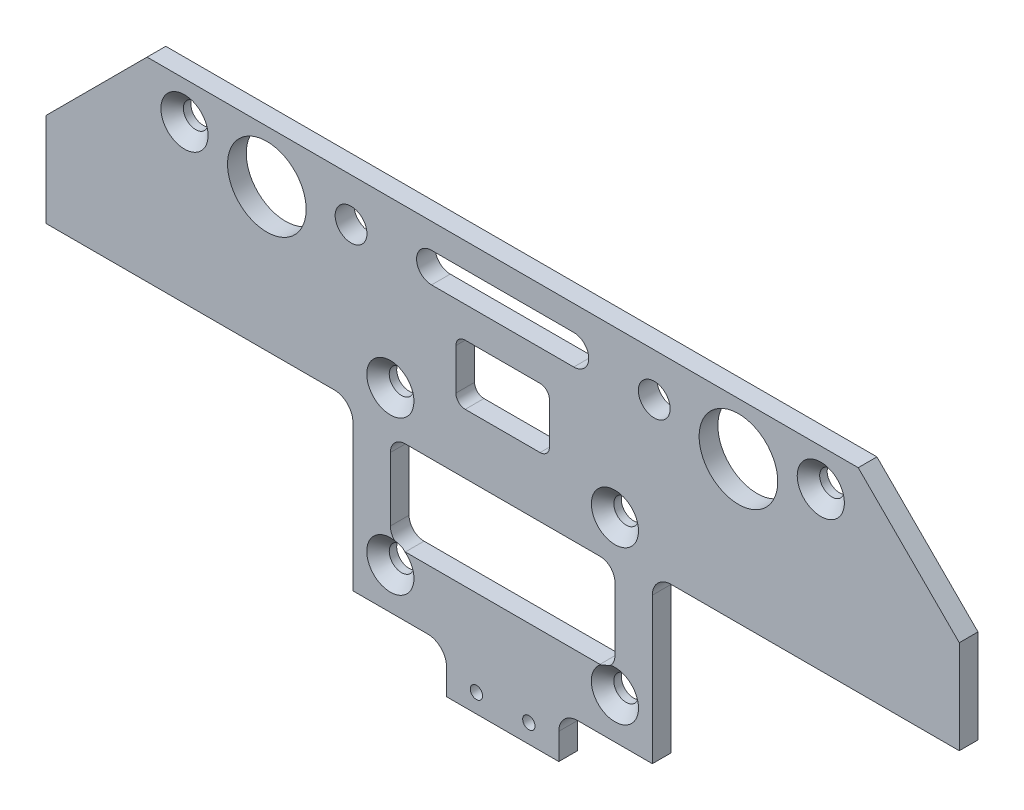
SolidWorks part; units mm, degrees
material "3.0205 (EN AW-1200)"
ref_plane "Plan de face" through (0, 0, 0) normal (0, 0, 1) x (1, 0, 0)
ref_plane "Plan de dessus" through (0, 0, 0) normal (0, 1, 0) x (1, 0, 0)
ref_plane "Plan de droite" through (0, 0, 0) normal (1, 0, 0) x (0, 0, -1)
sketch "Esquisse1" plane through (0, 0, 0) normal (0, 0, 1) x (1, 0, 0)
  line L0 (0, 0) -> (0, -52)
  line L1 (0, 0) -> (190, 0)
  line L2 (190, 0) -> (190, -52)
  line L3 (190, -52) -> (135, -52)
  line L4 (135, -52) -> (135, -96)
  line L5 (110, -108) -> (80, -108)
  line L6 (55, -96) -> (55, -52)
  line L7 (55, -52) -> (0, -52)
  line L9 (55, -96) -> (80, -96)
  line L12 (80, -96) -> (80, -108)
  line L13 (82.5, -23) -> (107.5, -23)
  line L14 (82.5, -23) -> (82.5, -39)
  line L15 (82.5, -39) -> (107.5, -39)
  line L16 (107.5, -23) -> (107.5, -39)
  line L17 (65, -55) -> (125, -55)
  line L18 (65, -55) -> (65, -80)
  line L19 (65, -80) -> (125, -80)
  line L20 (125, -55) -> (125, -80)
  line L21 (76, -6.71) -> (114, -6.71)
  line L22 (135, -96) -> (110, -96)
  line L23 (76, -14.71) -> (114, -14.71)
  line L26 (110, -96) -> (110, -108)
  arc A0 (114, -6.71) -> (114, -14.71) centre (114, -10.71) cw
  arc A1 (76, -6.71) -> (76, -14.71) centre (76, -10.71) ccw
  dimension "D21" = 38
  dimension "D23" = 12
  dimension "D1" = 190
  dimension "D2" = 52
  dimension "D3" = 52
  dimension "D4" = 55
  dimension "D5" = 55
  dimension "D6" = 30
  dimension "D8" = 25
  dimension "D9" = 108
  dimension "D10" = 12
  dimension "D11" = 16
  dimension "D12" = 39
  dimension "D13" = 25
  dimension "D14" = 82.5
  dimension "D15" = 25
  dimension "D16" = 80
  dimension "D17" = 65
  dimension "D18" = 65
  dimension "D19" = 14.71
  dimension "D20" = 6.71
  dimension "D22" = 76
extrude "Boss.-Extru.1" add sketch "Esquisse1" along normal blind 5
fillet "Congé1" radius 2.5 4 edges at (82.5, -39, 2.5) (107.5, -39, 2.5) (107.5, -23, 2.5) (82.5, -23, 2.5)
fillet "Congé2" radius 4 4 edges at (125, -80, 2.5) (125, -55, 2.5) (65, -55, 2.5) (65, -80, 2.5)
fillet "Congé3" radius 5 2 edges at (55, -52, 2.5) (135, -52, 2.5)
hole_wizard "Dégagement M61" positions "Esquisse3" profile "Esquisse2" hole size "M6" standard "ISO" end condition through all
sketch "Esquisse3" plane through (0, 0, 5) normal (0, 0, 1) x (1, 0, 0)
  line L0 (190, 0) -> (0, 0) construction
  line L3 (190, -52) -> (190, 0) construction
  line L4 (0, 0) -> (0, -52) construction
  point P12 (10, -10)
  point P14 (180, -10)
  dimension "D13" = 10
  dimension "D14" = 10
  dimension "D15" = 10
  dimension "D16" = 10
sketch "Esquisse2" plane through (10, -10, 5) normal (1, 0, 0) x (0, -1, 0)
  line L0 (0, 0) -> (0, 5)
  line L1 (0, 5) -> (3.3, 5)
  line L2 (3.3, 5) -> (3.3, 0)
  line L5 (3.3, 0) -> (0, 0)
  line L11 (0, -6.35) -> (0, 107.95) construction
  dimension "Diamètre du perçage jusqu'au prochain" = 6.6
  dimension "Profondeur du perçage jusqu'au prochain" = 5
hole_wizard "Dégagement M201" positions "Esquisse5" profile "Esquisse4" hole size "M20" standard "Ansi Métrique" end condition through all
sketch "Esquisse5" plane through (0, 0, 5) normal (0, 0, 1) x (1, 0, 0)
  line L0 (190, 0) -> (0, 0) construction
  line L1 (190, -52) -> (190, 0) construction
  line L2 (0, 0) -> (0, -52) construction
  point P0 (32, -14)
  point P1 (158, -14)
  dimension "D1" = 14
  dimension "D2" = 14
  dimension "D3" = 32
  dimension "D4" = 32
sketch "Esquisse4" plane through (32, -14, 5) normal (1, 0, 0) x (0, -1, 0)
  line L0 (0, 0) -> (0, 5)
  line L1 (0, 5) -> (10.5, 5)
  line L2 (10.5, 5) -> (10.5, 0)
  line L5 (10.5, 0) -> (0, 0)
  line L11 (0, -6.35) -> (0, 107.95) construction
  dimension "Diamètre du perçage jusqu'au prochain" = 21
  dimension "Profondeur du perçage jusqu'au prochain" = 5
sketch "Esquisse11" plane through (0, 0, 5) normal (0, 0, 1) x (1, 0, 0)
  line L0 (0, 0) -> (0, -52) construction
  line L1 (190, 0) -> (0, 0) construction
  circle A1 centre (54.5, -11.5) radius 4.25
  circle A2 centre (135.5, -11.5) radius 4.25
  dimension "D1" = 8.5
  dimension "D2" = 8.5
  dimension "D3" = 81
  dimension "D4" = 54.5
  dimension "D5" = 11.5
  dimension "D6" = 11.5
extrude "Enlèv. mat.-Extru.1" cut sketch "Esquisse11" against normal up to next
sketch "Esquisse13" plane through (0, 0, 5) normal (0, 0, 1) x (1, 0, 0)
  line L0 (0, 0) -> (-27, -27)
  line L1 (-27, -52) -> (0, -52)
  line L2 (217, -52) -> (190, -52)
  line L3 (0, 0) -> (0, -52) construction
  line L4 (190, 0) -> (0, 0) construction
  line L7 (190, 0) -> (217, -27)
  line L10 (0, 0) -> (0, -52)
  line L11 (190, 0) -> (190, -52)
  line L15 (217, -27) -> (217, -52)
  line L19 (-27, -27) -> (-27, -52)
  dimension "D1" = 135
  dimension "D2" = 27
  dimension "D3" = 27
  dimension "D5" = 135
extrude "Boss.-Extru.2" add sketch "Esquisse13" against normal blind 5
hole_wizard "Dégagement M62" positions "Esquisse23" profile "Esquisse22" hole size "M6" standard "ISO"
sketch "Esquisse23" plane through (0, 0, 5) normal (0, 0, 1) x (1, 0, 0)
  line L0 (55, -96) -> (80, -96) construction
  line L1 (110, -96) -> (135, -96) construction
  line L2 (-27, -27) -> (-27, -52) construction
  line L3 (217, -52) -> (217, -27) construction
  line L4 (135, -96) -> (135, -57) construction
  line L5 (55, -57) -> (55, -96) construction
  point P0 (65, -44)
  point P1 (125, -44)
  point P3 (125, -85)
  point P5 (65, -85)
  dimension "D1" = 52
  dimension "D2" = 52
  dimension "D3" = 92
  dimension "D4" = 92
  dimension "D5" = 10
  dimension "D6" = 10
  dimension "D7" = 11
  dimension "D8" = 11
sketch "Esquisse22" plane through (65, -44, 5) normal (1, 0, 0) x (0, -1, 0)
  line L0 (0, 0) -> (0, 6.9828)
  line L1 (0, 6.9828) -> (3.3, 5)
  line L2 (3.3, 5) -> (3.3, 0)
  line L5 (3.3, 0) -> (0, 0)
  line L10 (0, 6.9828) -> (-3.3, 5) construction
  line L11 (0, -6.35) -> (0, 107.95) construction
  dimension "Diamètre du perçage" = 6.6
  dimension "Profondeur du perçage" = 5
  dimension "Angle de pointe" = 118
fillet "Congé4" radius 5 2 edges at (80, -96, 2.5) (110, -96, 2.5)
hole_wizard "Trou taraudé M4x0.71" positions "Esquisse27" profile "Esquisse26" tap size "M4x0.7" standard "Ansi Métrique" end condition through all
sketch "Esquisse27" plane through (0, 0, 5) normal (0, 0, 1) x (1, 0, 0)
  line L0 (80, -101) -> (80, -108) construction
  line L1 (80, -108) -> (110, -108) construction
  line L2 (110, -108) -> (110, -101) construction
  point P0 (88, -103)
  point P2 (80, -104.5)
  point P7 (102, -103)
  dimension "D1" = 8
  dimension "D2" = 5
  dimension "D3" = 5
  dimension "D4" = 8
cosmetic thread "Filetage de perçage1" parameters "D2"=4
cosmetic thread "Filetage de perçage2" parameters "D2"=4
sketch "Esquisse26" plane through (88, -103, 5) normal (1, 0, 0) x (0, -1, 0)
  line L0 (0, 0) -> (0, 5)
  line L1 (0, 5) -> (1.65, 5)
  line L2 (1.65, 5) -> (1.65, 0)
  line L5 (1.65, 0) -> (0, 0)
  line L11 (0, -6.35) -> (0, 107.95) construction
  dimension "Diamètre du trou pour taraudage jusqu'au prochain" = 3.3
  dimension "Profondeur du trou pour taraudage jusqu'au prochain" = 5
chamfer "Chanfrein1" distance 3 angle 45 6 edges at (183.3, -10, 5) (13.3, -10, 5) (128.3, -85, 5) (68.3, -85, 5) (128.3, -44, 5) (68.3, -44, 5)
